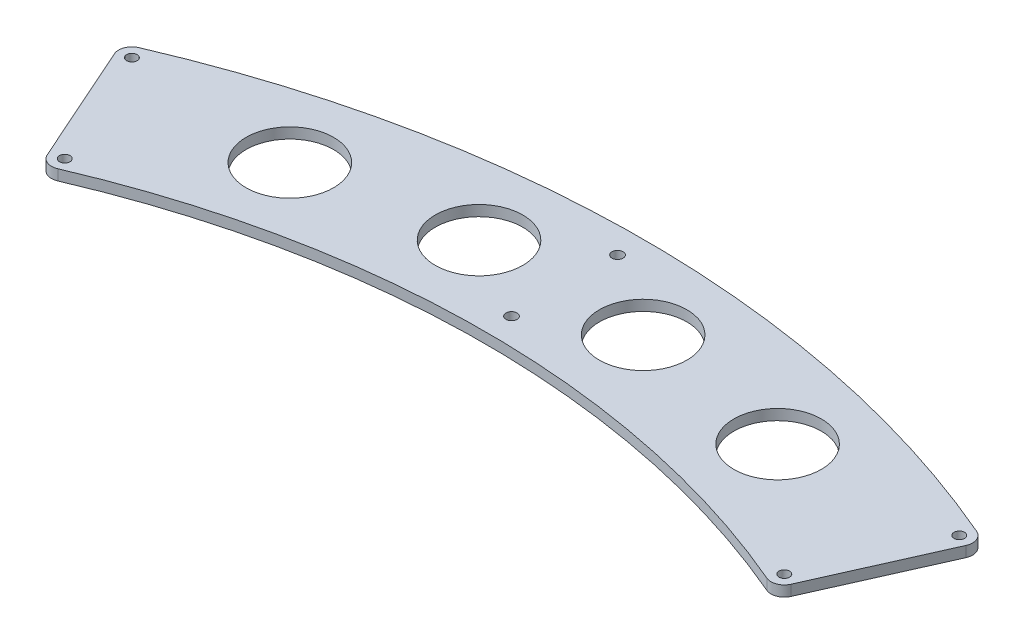
SolidWorks part; units mm, degrees
ref_plane "Спереди" through (0, 0, 0) normal (0, 0, 1) x (1, 0, 0)
ref_plane "Сверху" through (0, 0, 0) normal (0, 1, 0) x (1, 0, 0)
ref_plane "Справа" through (0, 0, 0) normal (1, 0, 0) x (0, 0, -1)
sketch "Эскиз1" plane through (0, 0, 0) normal (0, 1, 0) x (1, 0, 0)
  line L0 (30.9608, 368.7024) -> (0, 0) construction
  line L1 (0, 0) -> (0, 400) construction
  line L3 (0, 0) -> (92.0153, 358.3758) construction
  line L5 (-30.9608, 368.7024) -> (0, 0) construction
  line L6 (-92.0153, 358.3758) -> (0, 0) construction
  line L7 (0, 370) -> (-28.8317, 370) construction
  line L8 (-162.6947, 365.4182) -> (0, 0) construction
  line L9 (0, 0) -> (162.6947, 365.4182) construction
  line L11 (-76.9273, 361.9146) -> (-49.8646, 367.667) construction
  line L13 (76.9273, 361.9146) -> (136.5015, 349.2517) construction
  line L14 (-162.6947, 365.4182) -> (-138.2905, 310.6055)
  line L15 (138.2905, 310.6055) -> (162.6947, 365.4182)
  arc A0 (156.3688, 335.3339) -> (-261.6295, 261.6295) centre (0, 0) ccw construction
  arc A1 (162.6947, 365.4182) -> (-162.6947, 365.4182) centre (0, 0) ccw
  arc A2 (138.2905, 310.6055) -> (-138.2905, 310.6055) centre (0, 0) ccw
  circle A3 centre (30.9608, 368.7024) radius 16.5
  circle A4 centre (-30.9608, 368.7024) radius 16.5
  circle A5 centre (92.0153, 358.3758) radius 16.5
  circle A6 centre (-92.0153, 358.3758) radius 16.5
  circle A7 centre (0, 350) radius 2.1
  circle A8 centre (0, 390) radius 2.1
  dimension "D2" = 340
  dimension "D3" = 400
  dimension "D4" = 33
  dimension "D11" = 40
  dimension "D12" = 4.2
  dimension "D7" = 9.6
  dimension "D8" = 9.6
  dimension "D15" = 370
  dimension "D5" = 24
  dimension "D6" = 24
  dimension "D9" = 9.6
sheet metal parameters "Листовой металл1" thickness 4 parameters "D1"=1.2, "Толщина"=4
base flange "Базовая кромка1" sketch "Эскиз1" thickness 4 reverse thickness direction no parameters "D1"=1.2
fillet "Скругление1" radius 5 4 edges at (-162.6947, -2, -365.4182) (-138.2905, -2, -310.6055) (162.6947, -2, -365.4182) (138.2905, -2, -310.6055)
sketch "Эскиз2" plane through (0, 0, 0) normal (0, 1, 0) x (1, 0, 0)
  circle A0 centre (156.0804, 362.8552) radius 2
  circle A1 centre (135.7417, 317.1738) radius 2
  circle A2 centre (-135.7417, 317.1738) radius 2
  circle A3 centre (-156.0804, 362.8552) radius 2
extrude "Вырез-Вытянуть1" cut sketch "Эскиз2" against normal blind 10 normal cut yes
flat pattern "Развертка1" [suppressed]
sketch "Сгиб-Линии1" plane through (0, 0, 0) normal (0, 1, 0) x (1, 0, 0)
sketch3d "Граничная рамка1" [suppressed]
  line L0 (-105.7369, 160.0484, 0) -> (154.0999, 114.2321, 0) construction
  line L1 (-89.9793, 249.4139, 0) -> (169.8575, 203.5977, 0) construction
  line L2 (-105.7369, 160.0484, 0) -> (-89.9793, 249.4139, 0) construction
  line L3 (154.0999, 114.2321, 0) -> (169.8575, 203.5977, 0) construction
